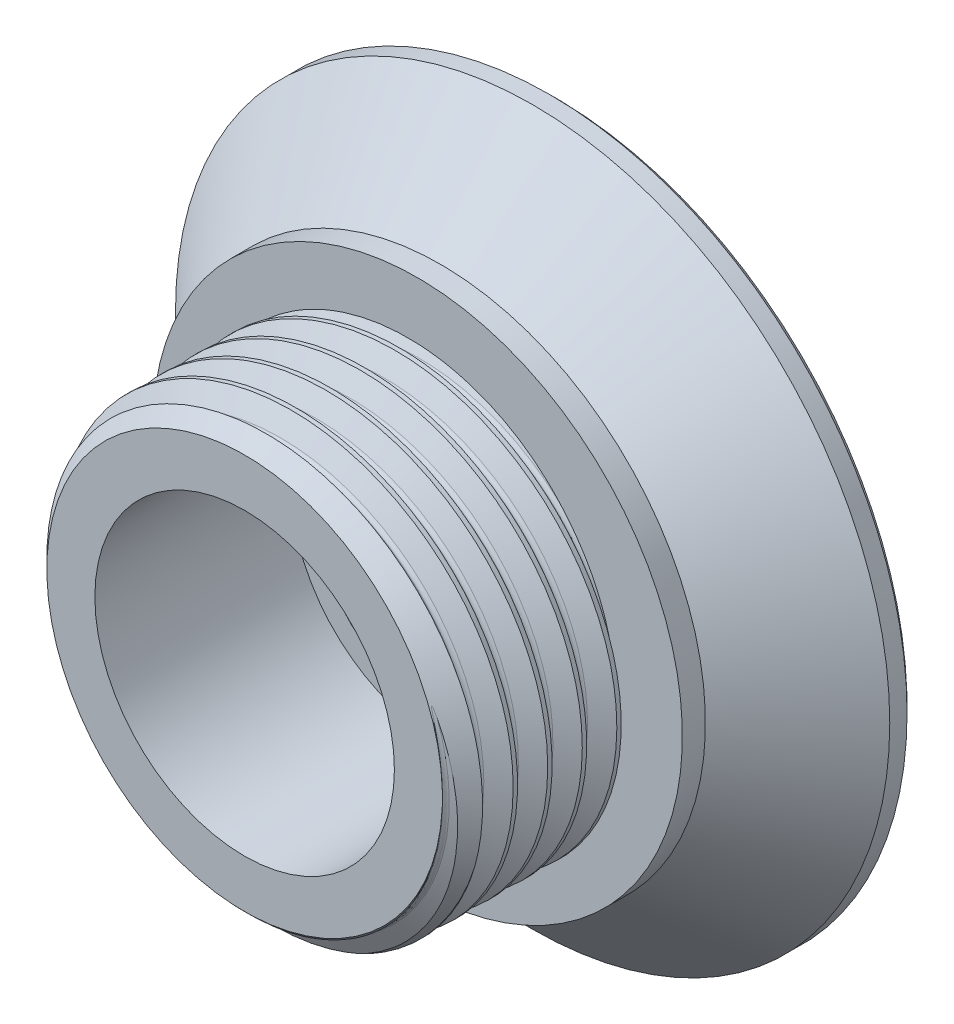
SolidWorks part; units mm, degrees
ref_plane "Front" through (0, 0, 0) normal (0, 0, 1) x (1, 0, 0)
ref_plane "Top" through (0, 0, 0) normal (0, 1, 0) x (1, 0, 0)
ref_plane "Right" through (0, 0, 0) normal (1, 0, 0) x (0, 0, -1)
sketch "Sketch1" plane through (0, 0, 0) normal (1, 0, 0) x (0, 0, -1)
  line L0 (-10, 11.1) -> (-3, 11.1)
  line L1 (-3, 11.1) -> (-3, 8.5)
  line L2 (-3, 8.5) -> (0, 8.5)
  line L3 (0, 8.5) -> (0, 31)
  line L4 (-10, 11.1) -> (-10, 13)
  line L5 (-10, 13) -> (-27, 13)
  line L6 (-10, 23) -> (-12, 23)
  line L7 (-12, 23) -> (-12, 17.17)
  line L8 (-12, 17.17) -> (-27, 17.17)
  line L9 (-27, 17.17) -> (-27, 13)
  line L10 (0, 0) -> (-61.0393, 0) construction
  line L11 (-2, 31) -> (-10, 23)
  line L12 (-2, 31) -> (0, 31)
  dimension "D1" = 17
  dimension "D2" = 3
  dimension "D3" = 45
  dimension "D4" = 2
  dimension "D5" = 2
  dimension "D6" = 46
  dimension "D7" = 22.2
  dimension "D8" = 26
  dimension "D9" = 15
  dimension "D10" = 34.34
  dimension "D12" = 62
revolve "Revolve1" add sketch "Sketch1" angle 360 about L10 region at (0, 18.1165, 8.5944)
sketch "Sketch2" plane through (0, 0, 12) normal (0, 0, 1) x (1, 0, 0)
  circle A0 centre (0, 0) radius 17.17 construction
  circle A1 centre (0, 0) radius 17.17
curve "Helix/Spiral1" pitch 3 height 18 radius 17.17 centre (0, 0, 12) axis (0, 0, 1) start towards (1, 0, 0)
sketch "Sketch3" plane through (0, 0, 0) normal (0, 1, 0) x (1, 0, 0)
  line L0 (17.1698, -27) -> (17.1698, -24.01)
  line L1 (17.5, -26.8329) -> (19.5, -25.6782) construction
  line L2 (17.3848, -24.3824) -> (18.9998, -25.3148)
  line L3 (18.9998, -25.3148) -> (18.9998, -25.6952)
  line L4 (18.9998, -25.6952) -> (17.3848, -26.6276)
  line L5 (18.9998, -25.505) -> (17.1698, -25.505) construction
  line L6 (19.5, -25.3318) -> (17.5, -24.1771) construction
  line L7 (17.5, -24.1771) -> (17.5, -23.453) construction
  line L8 (17.5, -26.8329) -> (17.5, -27.6765) construction
  line L9 (0, 0) -> (0, -31.2408) construction
  line L10 (18.9998, -25.3148) -> (19.0292, -25.3318) construction
  line L11 (19.0292, -25.6782) -> (18.9998, -25.6952) construction
  arc A0 (17.1698, -24.01) -> (17.3848, -24.3824) centre (17.5998, -24.01) ccw
  arc A1 (17.3848, -26.6276) -> (17.1698, -27) centre (17.5998, -27) ccw
  arc A2 (19.5, -25.6782) -> (19.5, -25.3318) centre (19.4, -25.505) ccw construction
  arc A3 (19.0292, -25.3318) -> (19.0292, -25.6782) centre (18.9292, -25.505) cw construction
  dimension "D1" = 0.43
  dimension "D5" = 0.2
  dimension "D9" = 0.2
  dimension "D2" = 60
  dimension "D3" = 1.83
  dimension "D4" = 2.99
  dimension "D6" = 2.1
  dimension "D7" = 17.5
  dimension "D8" = 17.1698
  dimension "D10" = 1.9594
sweep "Sweep1" add profiles "Sketch3" path "Helix/Spiral1"
sketch "Sketch4" plane through (0, 0, 0) normal (0, 1, 0) x (1, 0, 0)
  line L0 (-23.975, -27) -> (33.9572, -27)
  line L1 (-23, -12) -> (23, -12) construction
  dimension "D1" = 15
extrude "Cut-Extrude1" cut sketch "Sketch4" against normal through all both and the other way through all flip side to cut
sketch "Sketch5" plane through (0, 0, 0) normal (0, 1, 0) x (1, 0, 0)
  line L0 (17.17, -27) -> (19.67, -27)
  line L1 (19.67, -27) -> (19.67, -24.5)
  line L2 (19.67, -24.5) -> (17.17, -27)
  line L5 (0, 0) -> (0, -41.7558) construction
  dimension "D1" = 45
  dimension "D2" = 2.5
revolve "Cut-Revolve1" cut sketch "Sketch5" angle 360 about L5
chamfer "Chamfer1" distance 0.5 angle 45 3 edges at (-8.5, 0, 0) (-31, 0, 0) (-8.5, 0, 3)
